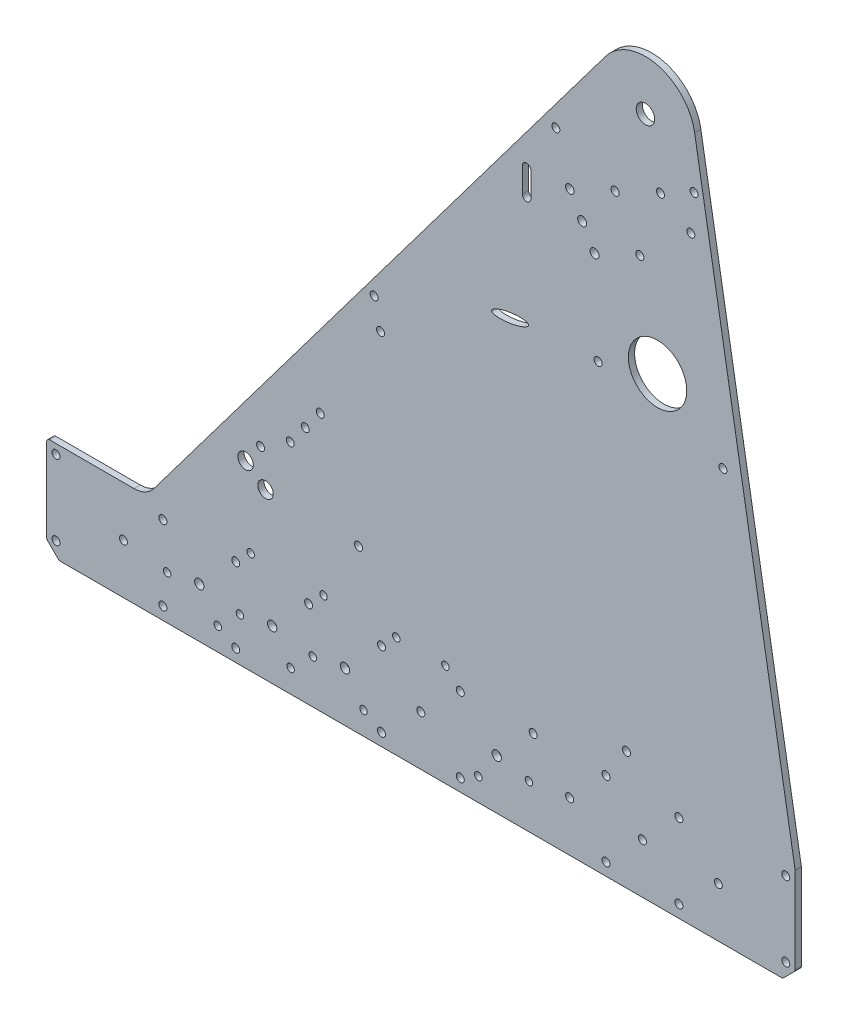
SolidWorks part; units mm, degrees
ref_plane "Front Plane" through (0, 0, 0) normal (0, 0, 1) x (1, 0, 0)
ref_plane "Top Plane" through (0, 0, 0) normal (0, 1, 0) x (1, 0, 0)
ref_plane "Right Plane" through (0, 0, 0) normal (1, 0, 0) x (0, 0, -1)
sketch "Sketch1" plane through (0, 0, 0) normal (0, 0, 1) x (1, 0, 0)
  line L1 (0, 0) -> (381, 0)
  line L2 (0, 0) -> (0, 50.8)
  line L4 (381, 0) -> (381, 50.8)
  line L5 (381, 50.8) -> (329.8374, 350.3513)
  line L6 (0, 50.8) -> (44.463, 50.8)
  line L11 (54.6105, 55.8634) -> (284.5049, 361.3482)
  arc A0 (284.5049, 361.3482) -> (329.8374, 350.3513) centre (304.8, 346.075) cw
  arc A1 (44.463, 50.8) -> (54.6105, 55.8634) centre (44.463, 63.5) ccw
  point P11 (50.8, 50.8)
  dimension "D4" = 346.075
  dimension "D7" = 12.7
  dimension "D5" = 25.4
  dimension "D1" = 50.8
  dimension "D2" = 381
  dimension "D3" = 76.2
  dimension "D6" = 50.8
extrude "Boss-Extrude1" add sketch "Sketch1" along normal blind 3.175
sketch "Sketch2" plane through (0, 0, 3.175) normal (0, 0, 1) x (1, 0, 0)
  line L1 (190.5, 50.8) -> (190.5, 0) construction
  line L3 (0, 0) -> (381, 0) construction
  line L5 (0, 6.35) -> (0, 0)
  line L6 (0, 50.8) -> (0, 0) construction
  line L7 (0, 0) -> (6.35, 0)
  line L8 (6.35, 0) -> (0, 6.35)
  line L9 (381, 0) -> (374.65, 0)
  line L10 (374.65, 0) -> (381, 6.35)
  line L11 (381, 6.35) -> (381, 0)
  circle A19 centre (4.7625, 46.0375) radius 2.032
  circle A20 centre (4.7625, 7.9375) radius 2.032
  circle A21 centre (376.2375, 7.9375) radius 2.032
  circle A22 centre (376.2375, 46.0375) radius 2.032
  dimension "D21" = 6.35
  dimension "D27" = 4.064
  dimension "D4" = 46.0375
  dimension "D22" = 6.35
  dimension "D25" = 4.7625
  dimension "D28" = 7.9375
extrude "Cut-Extrude1" cut sketch "Sketch2" against normal up to next
sketch "Sketch5" plane through (0, 0, 3.175) normal (0, 0, 1) x (1, 0, 0)
  line L0 (151.892, 25.4) -> (229.108, 25.4) construction
  line L1 (229.108, 25.4) -> (341.884, 25.4) construction
  circle A0 centre (39.116, 25.4) radius 2.032
  circle A1 centre (59.182, 6.35) radius 2.032
  circle A2 centre (59.182, 44.45) radius 2.032
  circle A3 centre (96.266, 44.45) radius 2.032
  circle A4 centre (133.35, 44.45) radius 2.032
  circle A5 centre (170.434, 44.45) radius 2.032
  circle A6 centre (210.566, 44.45) radius 2.032
  circle A7 centre (210.566, 6.35) radius 2.032
  circle A8 centre (170.434, 6.35) radius 2.032
  circle A9 centre (247.65, 44.45) radius 2.032
  circle A10 centre (266.192, 25.4) radius 2.032
  circle A11 centre (39.116, 25.4) radius 2.286 construction
  circle A12 centre (59.182, 44.45) radius 1.905 construction
  circle A13 centre (59.182, 6.35) radius 1.905 construction
  circle A14 centre (96.266, 44.45) radius 1.905 construction
  circle A15 centre (133.35, 44.45) radius 1.905 construction
  circle A16 centre (170.434, 44.45) radius 1.905 construction
  circle A17 centre (170.434, 6.35) radius 2.159 construction
  circle A18 centre (210.566, 6.35) radius 2.159 construction
  circle A19 centre (210.566, 44.45) radius 1.905 construction
  circle A20 centre (247.65, 44.45) radius 1.905 construction
  circle A21 centre (266.192, 25.4) radius 2.286 construction
  circle A22 centre (77.724, 25.4) radius 2.3813
  circle A23 centre (114.808, 25.4) radius 2.3813
  circle A24 centre (151.892, 25.4) radius 2.3813
  circle A25 centre (229.108, 25.4) radius 2.3813
  circle A26 centre (190.5, 25.4) radius 2.032
  circle A28 centre (303.276, 25.4) radius 2.032
  circle A29 centre (341.884, 25.4) radius 2.032
  circle A30 centre (77.724, 25.4) radius 7.366 construction
  circle A31 centre (114.808, 25.4) radius 7.366 construction
  circle A32 centre (151.892, 25.4) radius 7.366 construction
  circle A33 centre (229.108, 25.4) radius 7.366 construction
  dimension "D1" = 4.064
  dimension "D2" = 4.7625
  dimension "D3" = 37.084
  dimension "D4" = 38.608
  dimension "D5" = 38.608
extrude "Cut-Extrude4" cut sketch "Sketch5" against normal through all
sketch "Sketch6" plane through (0, 0, 3.175) normal (0, 0, 1) x (1, 0, 0)
  line L0 (6.35, 0) -> (374.65, 0) construction
  line L1 (266.192, 25.4) -> (303.276, 25.4) construction
  line L2 (284.734, 6.35) -> (284.734, 44.45) construction
  line L3 (151.892, 25.4) -> (114.808, 25.4) construction
  line L4 (114.808, 25.4) -> (77.724, 25.4) construction
  circle A0 centre (284.734, 44.45) radius 2.032
  circle A1 centre (284.734, 6.35) radius 2.032
  circle A2 centre (321.818, 6.35) radius 2.032
  circle A3 centre (321.818, 44.45) radius 2.032
  circle A4 centre (96.266, 6.35) radius 2.032
  circle A6 centre (295.148, 60.325) radius 2.032
  circle A7 centre (295.148, 60.325) radius 1.905 construction
  point P8 (284.734, 25.4)
  point P9 (284.734, 25.4)
  point P28 (96.266, 25.4)
  dimension "D1" = 4.064
  dimension "D2" = 6.35
  dimension "D3" = 37.084
extrude "Cut-Extrude5" cut sketch "Sketch6" against normal through all
sketch "Sketch3" plane through (0, 0, 3.175) normal (0, 0, 1) x (1, 0, 0)
  line L1 (381, 6.35) -> (381, 50.8) construction
  line L2 (6.35, 0) -> (374.65, 0) construction
  line L3 (304.8, 346.075) -> (289.3732, 304.3879) construction
  line L4 (266.2957, 293.7771) -> (289.3732, 304.3879) construction
  line L5 (266.2957, 293.7771) -> (272.5866, 282.7446) construction
  line L6 (272.5866, 282.7446) -> (278.8774, 271.7122) construction
  line L7 (381, 50.8) -> (329.8374, 350.3513) construction
  line L8 (244.3127, 279.4) -> (244.3127, 292.1) construction
  line L9 (0, 50.8) -> (0, 6.35) construction
  line L12 (284.5049, 361.3482) -> (54.6105, 55.8634) construction
  line L13 (242.1537, 279.4) -> (242.1537, 292.1)
  line L14 (246.4717, 279.4) -> (246.4717, 292.1)
  line L15 (194.5126, 212.725) -> (217.4224, 243.1676) construction
  line L16 (284.5049, 361.3482) -> (54.6105, 55.8634) construction
  circle A0 centre (304.8, 346.075) radius 4.699
  circle A1 centre (166.6875, 196.85) radius 2.032
  circle A2 centre (158.75, 82.55) radius 2.032
  circle A3 centre (289.3732, 304.3879) radius 2.0955
  circle A5 centre (266.2957, 293.7771) radius 2.159
  circle A6 centre (272.5866, 282.7446) radius 2.286
  circle A7 centre (278.8774, 271.7122) radius 2.286
  circle A8 centre (327.9008, 305.1149) radius 2.032
  circle A9 centre (344.223, 209.55) radius 2.032
  circle A12 centre (259.2118, 317.1783) radius 2.032
  arc A26 (242.1537, 279.4) -> (246.4717, 279.4) centre (244.3127, 279.4) ccw
  arc A27 (246.4717, 292.1) -> (242.1537, 292.1) centre (244.3127, 292.1) ccw
  circle A28 centre (217.4224, 243.1676) radius 2.032
  circle A29 centre (194.5126, 212.725) radius 2.032
  circle A30 centre (329.5323, 323.85) radius 2.032
  circle A35 centre (327.9008, 305.1149) radius 1.905 construction
  circle A36 centre (280.7072, 224.9429) radius 2.032
  circle A37 centre (280.7072, 224.9429) radius 1.905 construction
  point P27 (244.3127, 285.75)
  dimension "D1" = 9.398
  dimension "D3" = 4.064
  dimension "D6" = 4.064
  dimension "D11" = 4.318
  dimension "D10" = 4.191
  dimension "D13" = 4.064
  dimension "D20" = 4.064
  dimension "D18" = 2.159
  dimension "D28" = 17.4625
  dimension "D34" = 4.7625
  dimension "D21" = 38.1
  dimension "D19" = 9.525
  dimension "D29" = 4.064
  dimension "D33" = 4.064
  dimension "D31" = 4.572
  dimension "D4" = 222.25
  dimension "D5" = 82.55
  dimension "D7" = 25.4
  dimension "D8" = 12.7
  dimension "D9" = 44.45
  dimension "D12" = 12.7
  dimension "D14" = 135
  dimension "D15" = 9.525
  dimension "D16" = 85
  dimension "D17" = 209.55
  dimension "D22" = 12.7
  dimension "D23" = 53.975
  dimension "D24" = 6.35
  dimension "D25" = 196.85
  dimension "D26" = 166.6875
  dimension "D27" = 279.4
  dimension "D30" = 30
  dimension "D32" = 212.725
  dimension "D35" = 22.225
extrude "Cut-Extrude2" cut sketch "Sketch3" against normal through all
sketch "Sketch7" plane through (0, 0, 0) normal (0, 0, -1) x (-1, 0, 0)
  line L0 (-284.5049, 361.3482) -> (-54.6105, 55.8634) construction
  line L1 (-1.5875, 50.8) -> (-379.4125, 50.8) construction
  line L2 (-310.959, 234.5808) -> (-226.4577, 220.1482) construction
  line L3 (-381, 50.8) -> (-329.8374, 350.3513) construction
  line L4 (-139.2865, 131.4201) -> (-124.0133, 111.125) construction
  line L5 (-6.35, 0) -> (-374.65, 0) construction
  line L6 (-111.4089, 83.8159) -> (-101.2614, 91.4525) construction
  circle A0 centre (-310.959, 234.5808) radius 14.859
  circle A1 centre (-169.9907, 182.7803) radius 2.032
  circle A2 centre (-108.898, 101.6) radius 2.032
  circle A3 centre (-310.959, 234.5808) radius 15.113 construction
  circle A4 centre (-124.0133, 111.125) radius 2.032
  circle A5 centre (-131.6499, 121.2725) radius 2.032
  circle A6 centre (-139.2865, 131.4201) radius 2.032
  circle A7 centre (-101.2614, 91.4525) radius 3.937
  circle A11 centre (-111.4089, 83.8159) radius 3.937
  circle A14 centre (-312.4507, 314.9987) radius 2.032 construction
  circle A16 centre (-312.4507, 314.9987) radius 2.032
  circle A17 centre (-301.9549, 282.323) radius 2.032
  arc A18 (-299.7324, 282.323) -> (-304.1774, 282.323) centre (-301.9549, 282.323) ccw construction
  ellipse E0 centre (-235.8467, 221.7518) end of major axis (-245.2358, 223.3554) minor radius 2.3813
  point P36 (-131.6499, 121.2725)
  dimension "D1" = 29.718
  dimension "D2" = 4.064
  dimension "D7" = 4.064
  dimension "D11" = 25.4
  dimension "D12" = 4.064
  dimension "D16" = 7.874
  dimension "D3" = 15.875
  dimension "D4" = 15.875
  dimension "D5" = 101.6
  dimension "D6" = 50.8
  dimension "D8" = 4.7625
  dimension "D9" = 19.05
  dimension "D10" = 76.2
  dimension "D13" = 22.225
  dimension "D14" = 111.125
  dimension "D15" = 12.7
  dimension "D17" = 15.875
  dimension "D18" = 12.7
extrude "Cut-Extrude6" cut sketch "Sketch7" against normal through all
fillet "Fillet1" radius 1.5875 6 edges at (374.65, 0, 1.5875) (381, 6.35, 1.5875) (381, 50.8, 1.5875) (6.35, 0, 1.5875) (0, 6.35, 1.5875) (0, 50.8, 1.5875)
sketch "Sketch4" plane through (0, 0, 0) normal (0, 0, -1) x (-1, 0, 0)
  circle A0 centre (-61.3181, 22.2981) radius 1.905 construction
  circle A1 centre (-87.1313, 11.606) radius 1.905 construction
  circle A2 centre (-98.4021, 22.2981) radius 1.905 construction
  circle A3 centre (-124.2153, 11.606) radius 1.905 construction
  circle A4 centre (-135.4861, 22.2981) radius 1.905 construction
  circle A5 centre (-161.2993, 11.606) radius 1.905 construction
  circle A6 centre (-245.5139, 22.2981) radius 1.905 construction
  circle A7 centre (-219.7007, 11.606) radius 1.905 construction
  circle A8 centre (-202.982, 51.9684) radius 1.905 construction
  circle A9 centre (-178.018, 51.9684) radius 1.905 construction
  circle A10 centre (-140.934, 51.9684) radius 1.905 construction
  circle A11 centre (-103.85, 51.9684) radius 1.905 construction
  circle A12 centre (-61.3181, 22.2981) radius 1.905
  circle A13 centre (-87.1313, 11.606) radius 1.905
  circle A14 centre (-98.4021, 22.2981) radius 1.905
  circle A15 centre (-124.2153, 11.606) radius 1.905
  circle A16 centre (-135.4861, 22.2981) radius 1.905
  circle A17 centre (-161.2993, 11.606) radius 1.905
  circle A18 centre (-245.5139, 22.2981) radius 1.905
  circle A19 centre (-219.7007, 11.606) radius 1.905
  circle A20 centre (-202.982, 51.9684) radius 1.905
  circle A21 centre (-178.018, 51.9684) radius 1.905
  circle A22 centre (-140.934, 51.9684) radius 1.905
  circle A23 centre (-103.85, 51.9684) radius 1.905
extrude "Cut-Extrude3" cut sketch "Sketch4" against normal up to next
sketch "Sketch8" [suppressed] plane through (0, 0, 0) normal (0, 0, -1) x (-1, 0, 0)
  circle A0 centre (-139.2865, 131.4201) radius 2.032 construction
  circle A1 centre (-131.6499, 121.2725) radius 2.032 construction
  circle A2 centre (-124.0133, 111.125) radius 2.032 construction
  circle A5 centre (-139.2865, 131.4201) radius 2.032
  circle A6 centre (-131.6499, 121.2725) radius 2.032
  circle A7 centre (-124.0133, 111.125) radius 2.032
  circle A10 centre (-111.4089, 83.8159) radius 3.937 construction
  circle A11 centre (-101.2614, 91.4525) radius 3.937 construction
  circle A12 centre (-111.4089, 83.8159) radius 3.937
  circle A13 centre (-101.2614, 91.4525) radius 3.937
  ellipse E0 centre (-235.8467, 221.7518) end of major axis (-245.2358, 223.3554) minor radius 2.3813 construction
  ellipse E1 centre (-235.8467, 221.7518) end of major axis (-245.2358, 223.3554) minor radius 2.3813
extrude "Boss-Extrude2" [suppressed] add sketch "Sketch8" against normal up to surface (3.175 mm away) up to face at (63.2231, 22.2981, 3.175)
sketch "Sketch9" plane through (0, 0, 0) normal (0, 0, -1) x (-1, 0, 0)
  circle A0 centre (-194.5126, 212.725) radius 2.032 construction
  circle A1 centre (-217.4224, 243.1676) radius 2.032 construction
  circle A2 centre (-194.5126, 212.725) radius 2.032
  circle A3 centre (-217.4224, 243.1676) radius 2.032
extrude "Boss-Extrude3" add sketch "Sketch9" against normal up to surface (3.175 mm away) up to face at (63.2231, 22.2981, 3.175)
